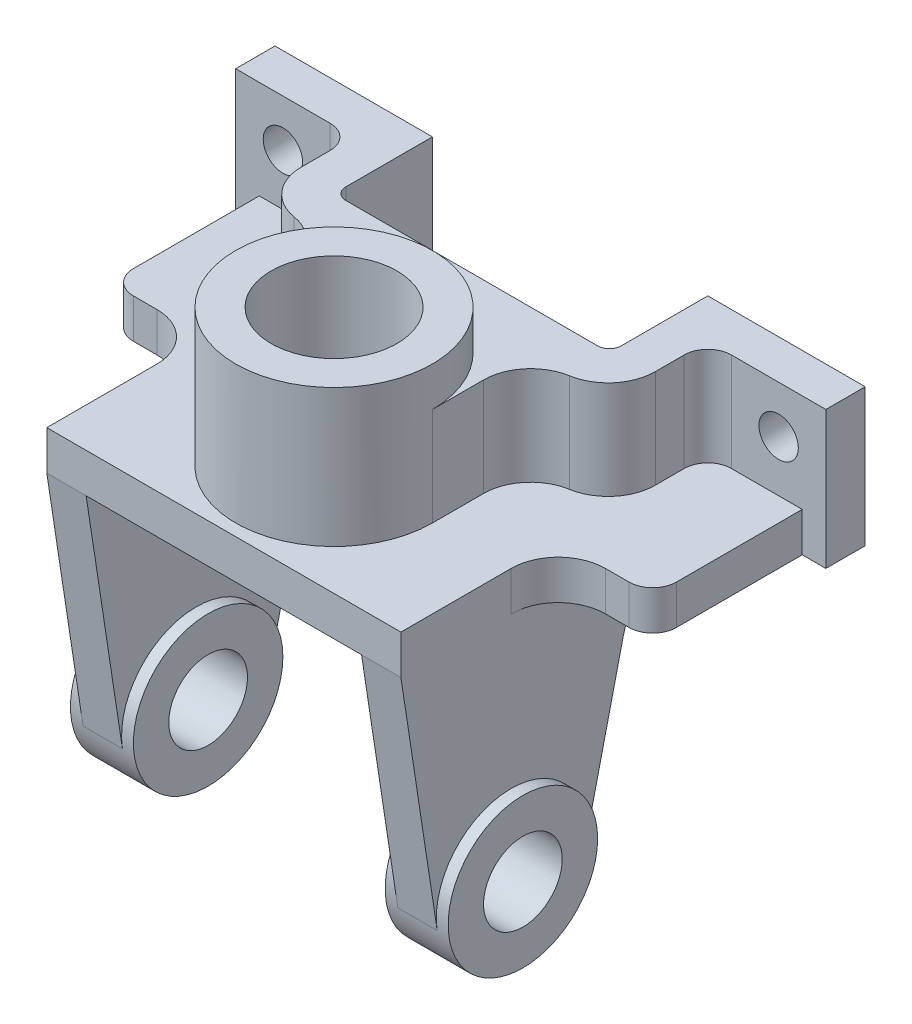
SolidWorks part; units mm, degrees
ref_plane "Front Plane" through (0, 0, 0) normal (0, 0, 1) x (1, 0, 0)
ref_plane "Top Plane" through (0, 0, 0) normal (0, 1, 0) x (1, 0, 0)
ref_plane "Right Plane" through (0, 0, 0) normal (1, 0, 0) x (0, 0, -1)
sketch "Sketch1" plane through (0, 0, 0) normal (0, 1, 0) x (1, 0, 0)
  line L0 (0, 0) -> (0, 60.9397) construction
  line L1 (0, 60.9397) -> (0, 0) construction
  line L2 (0, 0) -> (-91.3313, 0) construction
  line L3 (-32, 35) -> (32, 35)
  line L4 (35, 38) -> (35, 60)
  line L5 (35, 60) -> (75, 60)
  line L6 (75, 60) -> (75, 50)
  line L7 (75, 50) -> (51, 50)
  line L8 (45, 44) -> (45, 25)
  line L9 (45, 25) -> (37, 25)
  line L10 (25, 13) -> (25, 0)
  line L11 (57, 12) -> (63, 12)
  line L12 (69, 18) -> (69, 50)
  line L13 (45, 0) -> (45, -28)
  line L14 (-35, 38) -> (-35, 60)
  line L15 (-45, 0) -> (-45, -28)
  line L16 (-57, 12) -> (-63, 12)
  line L17 (-69, 18) -> (-69, 50)
  line L18 (-25, 13) -> (-25, 0)
  line L19 (-45, 25) -> (-37, 25)
  line L20 (-45, 44) -> (-45, 25)
  line L21 (-75, 50) -> (-51, 50)
  line L22 (-75, 60) -> (-75, 50)
  line L23 (-35, 60) -> (-75, 60)
  line L24 (-35, 35) -> (-35, 60)
  line L25 (-45, -28) -> (45, -28)
  circle A0 centre (0, 0) radius 25
  circle A1 centre (0, 0) radius 16
  arc A2 (-45, 44) -> (-51, 50) centre (-51, 44) ccw
  arc A3 (51, 50) -> (45, 44) centre (51, 44) ccw
  arc A4 (32, 35) -> (35, 38) centre (32, 38) ccw
  arc A5 (-32, 35) -> (-35, 38) centre (-32, 38) cw
  arc A6 (-25, 13) -> (-37, 25) centre (-37, 13) ccw
  arc A7 (37, 25) -> (25, 13) centre (37, 13) ccw
  arc A8 (-45, 0) -> (-57, 12) centre (-57, 0) ccw
  arc A9 (57, 12) -> (45, 0) centre (57, 0) ccw
  arc A10 (-63, 12) -> (-69, 18) centre (-63, 18) cw
  arc A11 (63, 12) -> (69, 18) centre (63, 18) ccw
  point P30 (-45, 50)
  point P33 (45, 50)
  point P36 (35, 35)
  point P42 (-25, 25)
  point P45 (25, 25)
  point P50 (-45, 12)
  point P53 (45, 12)
  point P56 (-69, 12)
  point P59 (69, 12)
  dimension "D11" = 50
  dimension "D12" = 32
  dimension "D13" = 6
  dimension "D14" = 3
  dimension "D15" = 12
  dimension "D17" = 12
  dimension "D18" = 6
  dimension "D1" = 70
  dimension "D2" = 90
  dimension "D3" = 150
  dimension "D4" = 10
  dimension "D5" = 60
  dimension "D6" = 10
  dimension "D7" = 25
  dimension "D8" = 38
  dimension "D9" = 69
  dimension "D10" = 90
  dimension "D16" = 40
extrude "Boss-Extrude1" add sketch "Sketch1" along normal blind 10 contours L11 A11 L12 L7 A3 L8 L9 A7 L10 A0 L18 A6 L19 L20 A2 L21 L17 A10 L16 A8 L15 L25 L13 A9 region at (-60, 0, -48.4148)
extrude "Boss-Extrude2" add sketch "Sketch1<3>" along normal blind 45 contours A0 A1 region at (0, 0, -24.2929)
sketch "Sketch1<3>" plane through (0, 0, 0) normal (0, 1, 0) x (1, 0, 0) same geometry as "Sketch1"
extrude "Boss-Extrude3" add sketch "Sketch1<4>" along normal blind 35 contours A7 L9 L8 A3 L7 L6 L5 L4 A4 L3 A5 L14 L23 L22 L21 A2 L20 L19 A6 L18 A0 L10 region at (0, 0, -33.3845)
sketch "Sketch1<4>" plane through (0, 0, 0) normal (0, 1, 0) x (1, 0, 0) same geometry as "Sketch1"
fillet "Fillet1" radius 12 2 edges at (-45, 22.5, -25) (45, 22.5, -25)
sketch "Sketch2" plane through (45, 0, 0) normal (1, 0, 0) x (0, 0, -1)
  line L0 (-28, 0) -> (-18.7819, -60.3088)
  line L1 (18.4972, -61.7802) -> (33, 0)
  line L2 (18, 0) -> (50, 0) construction
  line L3 (0, -57.438) -> (0, 87.8649) construction
  line L4 (-28, 0) -> (60, 0)
  circle A0 centre (0, -57.438) radius 19
  circle A1 centre (0, -57.438) radius 10
  line M3 (-28, 0) -> (0, 0)
  dimension "D1" = 20
  dimension "D2" = 38
  dimension "D3" = 28
  dimension "D4" = 33
extrude "Boss-Extrude4" add sketch "Sketch2" against normal blind 10 contours A0 L3 L0 M3 | L3 A0 L1 L4 region at (45, -21.0161, 12.9673) region at (45, -20.9334, -14.6598)
extrude "Boss-Extrude5" add sketch "Sketch2<3>" along normal blind 3 and the other way blind 13 contours A1 A0 region at (45, -39.0285, 1.3988)
sketch "Sketch2<3>" plane through (45, 0, 0) normal (1, 0, 0) x (0, 0, -1) same geometry as "Sketch2"
fillet "Fillet2" radius 25 1 edges at (40, 0, -33)
mirror "Mirror1" about plane through (0, 0, 0) normal (1, 0, 0) of "Boss-Extrude4", "Boss-Extrude5", "Fillet2"
sketch "Sketch3" plane through (0, 0, -50) normal (0, 0, 1) x (1, 0, 0)
  line L0 (75, 0) -> (69, 0) construction
  circle A0 centre (63, 23) radius 5
  dimension "D1" = 10
  dimension "D2" = 23
  dimension "D3" = 63
extrude "Cut-Extrude1" cut sketch "Sketch3" against normal through all
mirror "Mirror2" about plane through (0, 0, 0) normal (1, 0, 0) of "Cut-Extrude1"
